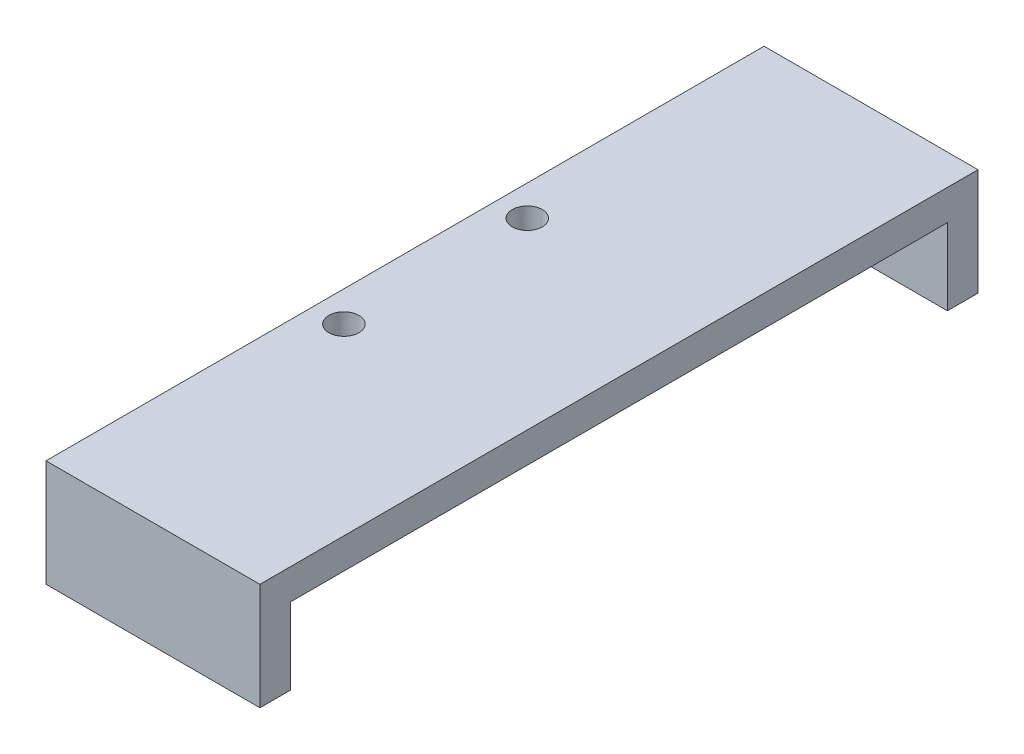
SolidWorks part; units mm, degrees
ref_plane "Front Plane" through (0, 0, 0) normal (0, 0, 1) x (1, 0, 0)
ref_plane "Top Plane" through (0, 0, 0) normal (0, 1, 0) x (1, 0, 0)
ref_plane "Right Plane" through (0, 0, 0) normal (1, 0, 0) x (0, 0, -1)
sketch "Sketch1" plane through (0, 0, 0) normal (1, 0, 0) x (0, 0, -1)
  line L0 (-27.305, 0) -> (27.305, 0)
  line L1 (27.305, 0) -> (27.305, -6.35)
  line L2 (-27.305, 0) -> (-27.305, -6.35)
  point P4 (0, 0)
  dimension "D1" = 54.61
  dimension "D2" = 6.35
extrude "Extrude-Thin1" add sketch "Sketch1" along normal blind 17.78 thin thin type one direction wall 2.54
sketch "Sketch2" plane through (0, 2.54, 0) normal (0, 1, 0) x (1, 0, 0)
  line L0 (0, 0) -> (17.78, 0) construction
  line L1 (17.78, 29.845) -> (17.78, -29.845) construction
  line L2 (2.54, -7.62) -> (2.54, 7.62) construction
  line L3 (0, 29.845) -> (0, -29.845) construction
  circle A0 centre (2.54, 7.62) radius 1.25
  circle A1 centre (2.54, -7.62) radius 1.25
  point P8 (2.54, 0)
  dimension "D1" = 2.5
  dimension "D3" = 2.54
extrude "Cut-Extrude1" cut sketch "Sketch2" against normal up to next
